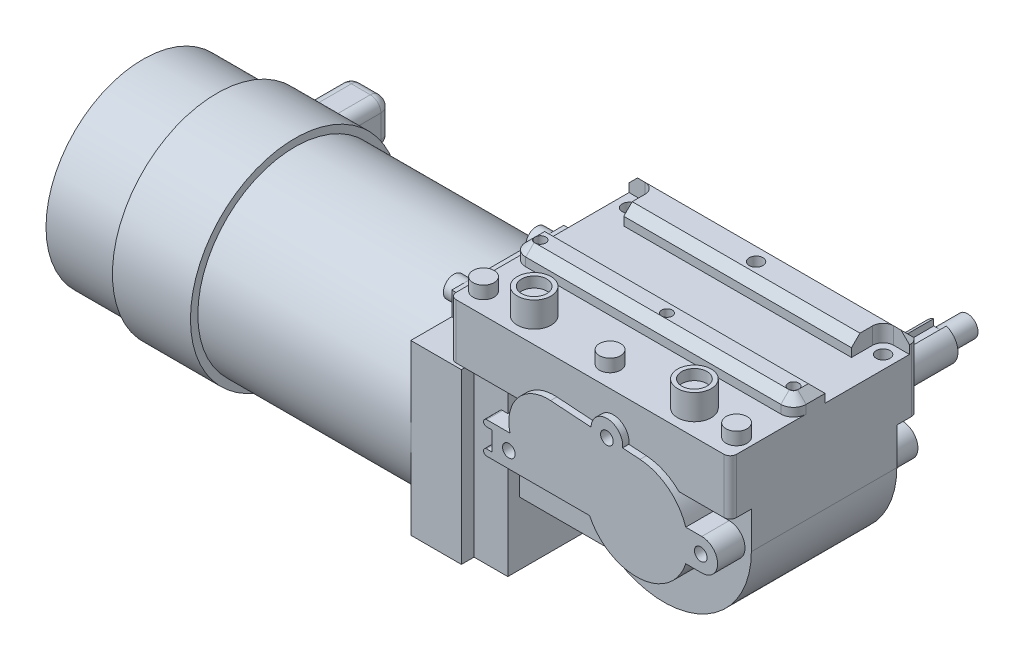
SolidWorks part; units mm, degrees
ref_plane "Front" through (0, 0, 0) normal (0, 0, 1) x (1, 0, 0)
ref_plane "Top" through (0, 0, 0) normal (0, 1, 0) x (1, 0, 0)
ref_plane "Right" through (0, 0, 0) normal (1, 0, 0) x (0, 0, -1)
sketch "Sketch1" plane through (0, 0, 0) normal (0, 1, 0) x (1, 0, 0)
  line L1 (-14.2998, 9.8999) -> (118.7002, 9.8999)
  line L2 (-14.2998, 9.8999) -> (-14.2998, -79.1001)
  line L3 (-14.2998, -79.1001) -> (118.7002, -79.1001)
  line L4 (118.7002, 9.8999) -> (118.7002, -79.1001)
extrude "Boss-Extrude1" add sketch "Sketch1" along normal blind 9 and the other way blind 17 contours L1 L4 L3 L2
sketch "Sketch2" plane through (0, 9, 0) normal (0, 1, 0) x (1, 0, 0)
  line L0 (118.7002, 9.8999) -> (118.7002, -79.1001) construction
  line L1 (-14.2998, -79.1001) -> (118.7002, -79.1001) construction
  line L2 (-14.2998, 9.8999) -> (-14.2998, -79.1001) construction
  circle A0 centre (111.7002, -69.1001) radius 5
  circle A1 centre (-8.2998, -69.1001) radius 5
  circle A2 centre (51.7002, -69.1001) radius 5
  dimension "D1" = 7
  dimension "D2" = 10
  dimension "D3" = 6
extrude "Boss-Extrude2" add sketch "Sketch2" along normal blind 6
sketch "Sketch3" plane through (0, 9, 0) normal (0, 1, 0) x (1, 0, 0)
  line L0 (-14.2998, -79.1001) -> (118.7002, -79.1001) construction
  circle A0 centre (89.7002, -67.1001) radius 8
  circle A1 centre (13.7002, -67.1001) radius 8
  circle A2 centre (111.7002, -69.1001) radius 5 construction
  circle A3 centre (-8.2998, -69.1001) radius 5 construction
  dimension "D1" = 12
  dimension "D3" = 22
  dimension "D4" = 22
  dimension "D2" = 12
extrude "Boss-Extrude3" add sketch "Sketch3" along normal blind 12
sketch "Sketch4" plane through (0, 21, 0) normal (0, 1, 0) x (1, 0, 0)
  circle A0 centre (89.7002, -67.1001) radius 6
  circle A1 centre (13.7002, -67.1001) radius 6
extrude "Cut-Extrude1" cut sketch "Sketch4" against normal blind 5
sketch "Sketch5" plane through (0, 9, 0) normal (0, 1, 0) x (1, 0, 0)
  line L0 (-14.2998, 9.8999) -> (-14.2998, -79.1001) construction
  line L1 (-14.2998, -34.1001) -> (118.7002, -34.1001)
  line L2 (-14.2998, -34.1001) -> (-14.2998, -43.1001)
  line L3 (-8.2998, -49.1001) -> (112.7002, -49.1001)
  line L4 (118.7002, -34.1001) -> (118.7002, -43.1001)
  line L5 (118.7002, 9.8999) -> (118.7002, -79.1001) construction
  line L6 (-14.2998, -79.1001) -> (118.7002, -79.1001) construction
  arc A0 (-14.2998, -43.1001) -> (-8.2998, -49.1001) centre (-8.2998, -43.1001) ccw
  arc A1 (112.7002, -49.1001) -> (118.7002, -43.1001) centre (112.7002, -43.1001) ccw
  point P15 (118.7002, -49.1001)
  dimension "D3" = 6
  dimension "D1" = 30
  dimension "D2" = 15
extrude "Boss-Extrude4" add sketch "Sketch5" along normal blind 8
sketch "Sketch6" plane through (0, 17, 0) normal (0, 1, 0) x (1, 0, 0)
  line L0 (118.7002, -43.1001) -> (118.7002, -34.1001) construction
  line L2 (-8.2998, -49.1001) -> (112.7002, -49.1001) construction
  line L6 (-14.2998, -34.1001) -> (-14.2998, -43.1001) construction
  circle A0 centre (112.2002, -42.6001) radius 2.5
  circle A1 centre (-7.7998, -42.6001) radius 2.5
  circle A2 centre (52.2002, -42.6001) radius 2.5
  dimension "D1" = 6.5
  dimension "D2" = 6.5
  dimension "D3" = 6.5
  dimension "D4" = 60
chamfer "Chamfer1" distance 4 angle 45 6 edges at (52.2002, 17, 34.1001) (-14.2998, 17, 38.6001) (118.7002, 17, 38.6001) (-12.5425, 17, 47.3427) (116.9428, 17, 47.3427) (52.2002, 17, 49.1001)
sketch "Sketch7" plane through (0, 9, 0) normal (0, 1, 0) x (1, 0, 0)
  line L0 (118.7002, 9.8999) -> (118.7002, -34.1001) construction
  line L1 (-14.2998, 9.8999) -> (118.7002, 9.8999)
  line L2 (-14.2998, 9.8999) -> (-14.2998, -9.1001)
  line L3 (-14.2998, -9.1001) -> (118.7002, -9.1001)
  line L4 (118.7002, 9.8999) -> (118.7002, -9.1001)
extrude "Boss-Extrude5" add sketch "Sketch7" along normal blind 8 contours L3 L4 L1 L2
chamfer "Chamfer2" distance 4 angle 45 4 edges at (52.2002, 17, -9.8999) (118.7002, 17, -0.3999) (52.2002, 17, 9.1001) (-14.2998, 17, -0.3999)
sketch "Sketch9" plane through (0, 17, 0) normal (0, 1, 0) x (1, 0, 0)
  line L0 (118.7002, 9.8999) -> (118.7002, -9.1001) construction
  line L1 (111.2002, 5.8999) -> (132.9628, 5.8999)
  line L2 (106.2002, 0.8999) -> (106.2002, -16.4675)
  line L3 (106.2002, -16.4675) -> (132.9628, -16.4675)
  line L4 (132.9628, 5.8999) -> (132.9628, -16.4675)
  line L5 (-14.2998, 9.8999) -> (118.7002, 9.8999) construction
  line L6 (-14.2998, -9.1001) -> (-14.2998, 9.8999) construction
  line L7 (-28.6746, 5.8999) -> (-6.7998, 5.8999)
  line L8 (-28.6746, 5.8999) -> (-28.6746, -10.6813)
  line L9 (-28.6746, -10.6813) -> (-1.7998, -10.6813)
  line L10 (-1.7998, 0.8999) -> (-1.7998, -10.6813)
  arc A0 (111.2002, 5.8999) -> (106.2002, 0.8999) centre (111.2002, 0.8999) ccw
  arc A1 (-6.7998, 5.8999) -> (-1.7998, 0.8999) centre (-6.7998, 0.8999) cw
  dimension "D3" = 5
  dimension "D6" = 5
  dimension "D1" = 12.5
  dimension "D2" = 4
  dimension "D4" = 12.5
  dimension "D5" = 4
extrude "Cut-Extrude2" cut sketch "Sketch9" against normal blind 8
sketch "Sketch10" plane through (0, 17, 0) normal (0, 1, 0) x (1, 0, 0)
  line L0 (118.7002, 5.8999) -> (118.7002, -34.1001) construction
  line L3 (-14.2998, 9.8999) -> (118.7002, 9.8999) construction
  line L4 (-14.2998, 5.8999) -> (-14.2998, -34.1001) construction
  line L5 (106.2002, 0.8999) -> (106.2002, -5.1001) construction
  line L10 (106.2002, 0.8999) -> (106.2002, -9.1001) construction
  line L11 (-1.7998, -9.1001) -> (-1.7998, 0.8999) construction
  circle A0 centre (112.4502, -0.3501) radius 3.25
  circle A1 centre (52.2002, -0.3501) radius 3.25
  circle A2 centre (-8.0498, -0.3501) radius 3.25
  dimension "D1" = 6.25
  dimension "D3" = 6.25
  dimension "D2" = 10.25
  dimension "D4" = 10.25
  dimension "D5" = 54
  dimension "D6" = 133
  dimension "D7" = 12.5
  dimension "D8" = 12.5
  dimension "D9" = 108
fillet "Fillet1" radius 3 4 edges at (118.7002, -2, -9.8999) (-14.2998, -2, -9.8999) (-14.2998, -4, 79.1001) (118.7002, -4, 79.1001)
sketch "Sketch11" plane through (0, 0, 79.1001) normal (0, 0, 1) x (1, 0, 0)
  line L0 (-11.2998, 9) -> (115.7002, 9) construction
  line L1 (-8.2998, 9) -> (112.7002, 9) construction
  line L2 (35.2002, -7) -> (35.2002, -44) construction
  line L3 (118.7002, 9) -> (118.7002, -17) construction
  line L5 (36.4816, -7.0444) -> (55.7011, -8.3789)
  line L6 (35.2002, -44) -> (35.2002, -45.0297) construction
  line L7 (8.7002, -45.0297) -> (55.0016, -45.0297)
  line L8 (8.7002, -45.0297) -> (6.2002, -45.0297)
  line L9 (8.7002, -42.0514) -> (8.7002, -33.008)
  line L10 (8.7002, -30.0297) -> (17.2633, -30.0297)
  line L11 (8.7002, -30.0297) -> (6.2002, -30.0297)
  line L12 (6.2002, -33.008) -> (8.7002, -33.008)
  line L13 (6.2002, -42.0514) -> (8.7002, -42.0514)
  line L14 (108.2002, -27) -> (100.5967, -27)
  line L15 (108.2002, -42) -> (100.5967, -42)
  line L16 (70.644, -9.4164) -> (78.9019, -9.9897)
  arc A0 (70.644, -9.4164) -> (55.7011, -8.3789) centre (63.2002, -8.5) ccw
  arc A1 (55.0016, -45.0297) -> (100.5967, -42) centre (77.2002, -34.5) ccw
  arc A2 (100.5967, -27) -> (78.9019, -9.9897) centre (77.2002, -34.5) ccw
  arc A3 (108.2002, -42) -> (108.2002, -27) centre (108.2002, -34.5) ccw
  arc A4 (6.2002, -42.0514) -> (6.2002, -45.0297) centre (6.2002, -43.5405) ccw
  arc A5 (6.2002, -30.0297) -> (6.2002, -33.008) centre (6.2002, -31.5188) ccw
  arc A6 (36.4816, -7.0444) -> (17.2633, -30.0297) centre (35.2002, -25.5) ccw
  dimension "D1" = 17.5
  dimension "D4" = 10.5
  dimension "D5" = 41.5
  dimension "D7" = 55.5
  dimension "D8" = 73
  dimension "D11" = 2.5
  dimension "D2" = 43.5
  dimension "D6" = 43.5
  dimension "D10" = 99.5
extrude "Boss-Extrude6" add sketch "Sketch11" against normal blind 92 and the other way blind 3
ref_plane "Plane1" through (0, 0, 69.1001) normal (0, 0, 1) x (1, 0, 0)
sketch "Sketch12" plane through (0, 0, 69.1001) normal (0, 0, 1) x (1, 0, 0)
  line L0 (118.7002, -14.3455) -> (118.7002, -34.5)
  line L1 (118.7002, 9) -> (118.7002, -17) construction
  line L2 (118.7002, -14.3455) -> (113.4775, -14.3455)
  line L4 (8.7002, -67.0297) -> (51.4306, -67.0297)
  line L5 (8.7002, -67.0297) -> (8.7002, -17)
  line L6 (-11.2998, -17) -> (18.7685, -17) construction
  line L7 (8.7002, -17) -> (39.5704, -17)
  arc A0 (51.4306, -67.0297) -> (118.7002, -34.5) centre (77.2002, -34.5) ccw
  arc A1 (113.4775, -14.3455) -> (39.5704, -17) centre (77.2002, -34.5) ccw
extrude "Boss-Extrude7" add sketch "Sketch12" against normal blind 69
sketch "Sketch13" plane through (0, 0, 82.1001) normal (0, 0, 1) x (1, 0, 0)
  line L0 (17.2633, -30.0297) -> (8.7002, -30.0297) construction
  line L1 (8.7002, -33.008) -> (8.7002, -42.0514) construction
  circle A0 centre (63.2002, -9.018) radius 3
  arc A2 (70.644, -9.4164) -> (55.7011, -8.3789) centre (63.2002, -8.5) ccw construction
  circle A4 centre (107.7002, -34.5) radius 3
  arc A7 (108.2002, -42) -> (108.2002, -27) centre (108.2002, -34.5) ccw construction
  circle A9 centre (16.7002, -37.5297) radius 3
  point P6 (63.7196, -1.018)
  point P17 (115.7002, -34.5)
  point P20 (8.7002, -37.5297)
  dimension "D1" = 8
  dimension "D2" = 0
  dimension "D3" = 8
  dimension "D4" = 7.5
  dimension "D5" = 8
sketch "Sketch14" plane through (0, 0, -12.8999) normal (0, 0, 1) x (1, 0, 0)
  circle A0 centre (63.2002, -9.018) radius 3
  circle A4 centre (107.7002, -34.5) radius 3
  circle A9 centre (16.7002, -37.5297) radius 3
extrude "Cut-Extrude3" cut sketch "Sketch13" against normal blind 16
extrude "Cut-Extrude7" cut sketch "Sketch14" along normal blind 16
sketch "Sketch15" plane through (8.7002, 0, 0) normal (-1, 0, 0) x (0, 0, 1)
  line L0 (-6.8999, -17) -> (76.1001, -17) construction
  line L1 (-5.3999, -17) -> (74.6001, -17)
  line L2 (-5.3999, -17) -> (-5.3999, -97)
  line L3 (-5.3999, -97) -> (74.6001, -97)
  line L4 (74.6001, -17) -> (74.6001, -97)
  point P4 (34.6001, -17)
  point P7 (34.6001, -17)
extrude "Boss-Extrude8" add sketch "Sketch15" along normal blind 16
sketch "Sketch16" plane through (-7.2998, 0, 0) normal (-1, 0, 0) x (0, 0, 1)
  line L0 (-6.8999, -17) -> (76.1001, -17) construction
  line L1 (-11.3999, -17) -> (8.0377, -17)
  line L2 (-11.3999, -17) -> (-11.3999, -97)
  line L3 (-11.3999, -97) -> (5.6001, -97)
  line L4 (80.6001, -17) -> (80.6001, -97)
  line L5 (61.1625, -17) -> (80.6001, -17)
  line L6 (63.6001, -97) -> (80.6001, -97)
  line L7 (8.0377, -17) -> (8.0377, -6)
  line L8 (8.0377, -6) -> (61.1625, -6)
  line L9 (61.1625, -17) -> (61.1625, -6)
  line L11 (5.6001, -97) -> (5.6001, -107)
  line L12 (5.6001, -107) -> (63.6001, -107)
  line L13 (63.6001, -97) -> (63.6001, -107)
extrude "Boss-Extrude9" add sketch "Sketch16" along normal blind 24 contours L2 L3 L11 L12 L13 L6 L4 L5 L9 L8 L7 L1
sketch "Sketch17" plane through (-31.2998, 0, 0) normal (-1, 0, 0) x (0, 0, 1)
  line L0 (80.6001, -17) -> (80.6001, -97) construction
  line L4 (61.1625, -6) -> (8.0377, -6) construction
  circle A0 centre (34.6001, -57) radius 46
  dimension "D1" = 51
  dimension "D2" = 92
extrude "Boss-Extrude10" add sketch "Sketch17" along normal blind 101
sketch "Sketch18" plane through (-132.2998, 0, 0) normal (-1, 0, 0) x (0, 0, 1)
  circle A0 centre (34.6001, -57) radius 49.5
  circle A1 centre (34.6001, -57) radius 46 construction
extrude "Boss-Extrude11" add sketch "Sketch18" along normal blind 37 contours A0
sketch "Sketch19" plane through (-169.2998, 0, 0) normal (-1, 0, 0) x (0, 0, 1)
  circle A0 centre (34.6001, -57) radius 46
  circle A1 centre (34.6001, -57) radius 49.5 construction
extrude "Boss-Extrude12" add sketch "Sketch19" along normal blind 35 contours A0
sketch "Sketch20" plane through (-169.2998, 0, 0) normal (-1, 0, 0) x (0, 0, 1)
  line L0 (-9.2177, -43) -> (-9.2177, -71)
  line L1 (-15.2177, -48) -> (-15.2177, -66)
  line L3 (-15.2177, -48) -> (-9.2177, -43)
  line L4 (-9.2177, -71) -> (-15.2177, -66)
  circle A0 centre (34.6001, -57) radius 46 construction
  circle A1 centre (34.6001, -57) radius 46 construction
  point P2 (-15.2177, -57)
  point P5 (-9.2177, -57)
extrude "Boss-Extrude13" add sketch "Sketch20" along normal blind 9
ref_plane "Plane3" through (-166.2998, 0, 0) normal (-1, 0, 0) x (0, 0, 1)
sketch "Sketch21" plane through (-166.2998, 0, 0) normal (-1, 0, 0) x (0, 0, 1)
  line L0 (-15.2177, -48) -> (-15.2177, -66) construction
  line L1 (-15.2177, -46.5) -> (-45.2177, -46.5)
  line L2 (-15.2177, -46.5) -> (-15.2177, -67.5)
  line L3 (-15.2177, -67.5) -> (-45.2177, -67.5)
  line L4 (-45.2177, -46.5) -> (-45.2177, -67.5)
  point P4 (-15.2177, -57)
  point P7 (-15.2177, -57)
extrude "Boss-Extrude14" add sketch "Sketch21" along normal blind 19
sketch "Sketch22" plane through (0, 0, -12.8999) normal (0, 0, -1) x (-1, 0, 0)
  circle A0 centre (-77.2002, -34.5) radius 10.5
  arc A1 (-100.5967, -42) -> (-55.0016, -45.0297) centre (-77.2002, -34.5) ccw construction
extrude "Boss-Extrude15" add sketch "Sketch22" along normal blind 3
sketch "Sketch23" plane through (0, 0, -15.8999) normal (0, 0, -1) x (-1, 0, 0)
  circle A0 centre (-77.2002, -34.5) radius 8.5
  circle A1 centre (-77.2002, -34.5) radius 10.5 construction
extrude "Boss-Extrude16" add sketch "Sketch23" along normal blind 46
sketch "Sketch24" plane through (0, 0, -61.8999) normal (0, 0, -1) x (-1, 0, 0)
  line L1 (-80.2002, -25.547) -> (-74.2002, -25.547)
  line L2 (-80.2002, -25.547) -> (-80.2002, -29.547)
  line L3 (-80.2002, -29.547) -> (-74.2002, -29.547)
  line L4 (-74.2002, -25.547) -> (-74.2002, -29.547)
extrude "Cut-Extrude8" cut sketch "Sketch24" against normal blind 42
extrude "Cut-Extrude10" cut sketch "Sketch6" against normal blind 14
extrude "Cut-Extrude11" cut sketch "Sketch10" against normal blind 30
sketch "Sketch26" plane through (0, 0, -61.8999) normal (0, 0, -1) x (-1, 0, 0)
  circle A0 centre (-77.2002, -34.5) radius 5
extrude "Boss-Extrude21" add sketch "Sketch26" along normal blind 13
sketch "Sketch27" plane through (-31.2998, 0, 0) normal (-1, 0, 0) x (0, 0, 1)
  line L0 (5.6001, -107) -> (63.6001, -107) construction
  line L1 (8.0377, -6) -> (61.1625, -6) construction
  line L2 (61.1625, -17) -> (61.1625, -6) construction
  line L3 (8.0377, -17) -> (8.0377, -6) construction
  line L4 (5.6001, -97) -> (5.6001, -107) construction
  line L5 (63.6001, -97) -> (63.6001, -107) construction
  circle A0 centre (54.1625, -11) radius 5
  circle A1 centre (15.0377, -11) radius 5
  circle A2 centre (56.6001, -102) radius 5
  circle A3 centre (12.6001, -102) radius 5
  point P15 (61.1625, -11.5)
  dimension "D1" = 7
  dimension "D2" = 7
  dimension "D3" = 7
  dimension "D4" = 7
extrude "Boss-Extrude22" add sketch "Sketch27" along normal blind 6
fillet "Fillet3" radius 5 3 edges at (-166.2998, -46.5, -30.2177) (-175.7998, -46.5, -45.2177) (-185.2998, -46.5, -30.2177)
fillet "Fillet4" radius 5 10 edges at (-167.7643, -47.9645, -43.7532) (-183.8354, -47.9645, -43.7532) (-185.2998, -59.5, -15.2177) (-185.2998, -67.5, -30.2177) (-175.7998, -67.5, -45.2177) (-166.2998, -59.5, -45.2177) (-185.2998, -59.5, -45.2177) (-166.2998, -59.5, -15.2177) (-175.7998, -46.5, -15.2177) (-183.8354, -47.9645, -15.2177)
fillet "Fillet6" radius 5 5 edges at (-167.7643, -66.0355, -43.7532) (-166.2998, -67.5, -30.2177) (-183.8354, -66.0355, -16.6822) (-175.7998, -67.5, -15.2177) (-167.7643, -67.5, -16.6822)
